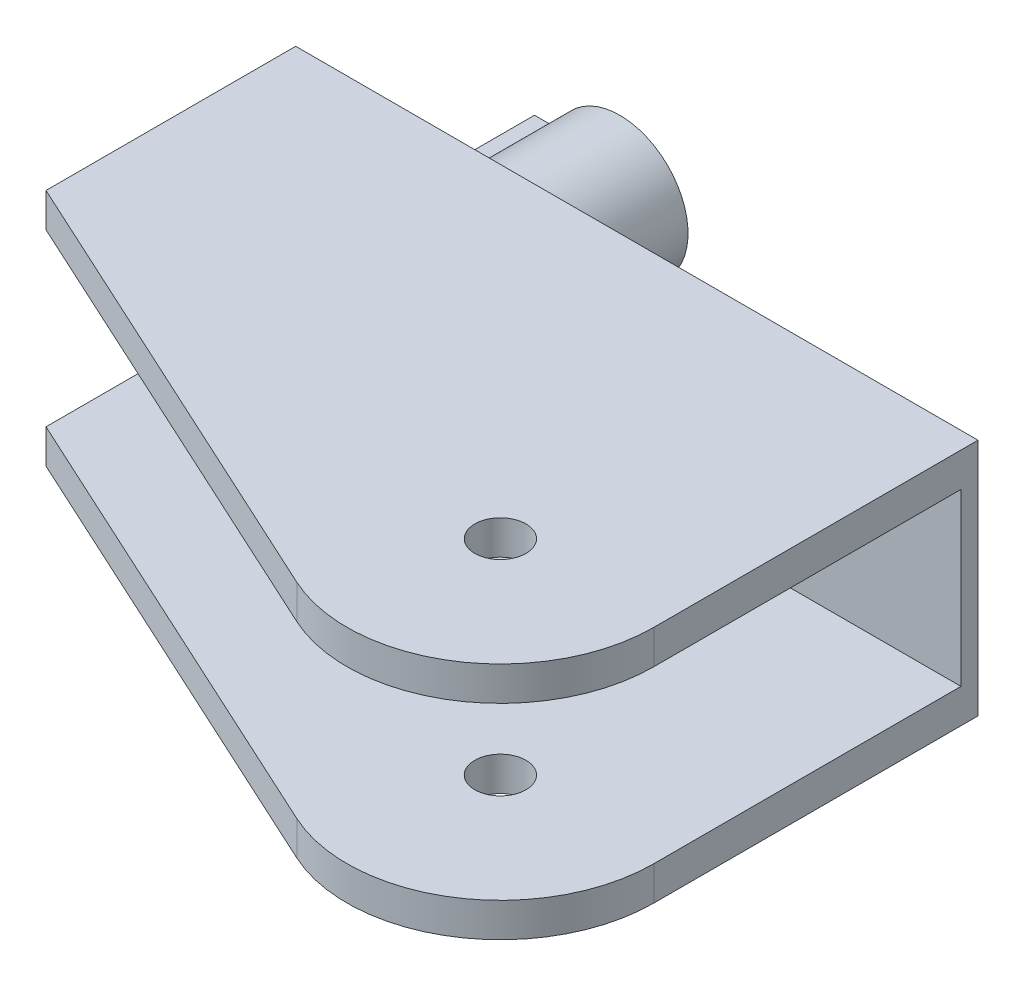
SolidWorks part; units mm, degrees
note: '?' marks a value the reader was unsure of. The reader was unsure of these and kept them because the rebuilt part matched: shared geometry of "草图1<2>".
ref_plane "前视基准面" through (0, 0, 0) normal (0, 0, 1) x (1, 0, 0)
ref_plane "上视基准面" through (0, 0, 0) normal (0, 1, 0) x (1, 0, 0)
ref_plane "右视基准面" through (0, 0, 0) normal (1, 0, 0) x (0, 0, -1)
other "Configuration Table"
sketch "草图1" plane through (0, 0, 0) normal (0, 1, 0) x (1, 0, 0)
  line L0 (45, 0) -> (45, 90)
  line L1 (45, 90) -> (-155, 90)
  line L2 (-155, 90) -> (-155, 21.8046)
  line L3 (-155, 21.8046) -> (-18.815, -40.8778)
  arc A0 (-18.815, -40.8778) -> (45, 0) centre (0, 0) ccw
  circle A1 centre (0, 0) radius 7.5
  dimension "D1" = 15
  dimension "D2" = 90
  dimension "D3" = 200
  dimension "D4" = 90
extrude "凸台-拉伸1" add sketch "草图1" along normal blind 10
ref_plane "基准面1" through (0, -25, 0) normal (0, -1, 0) x (-1, 0, 0)
sketch "草图3" plane through (45, 0, 0) normal (1, 0, 0) x (0, 0, -1)
  line L0 (-74.25, -25) -> (74.25, -25) construction
  line L5 (90, 10) -> (95, 10)
  line L6 (90, 10) -> (90, -25)
  line L7 (90, -25) -> (95, -25)
  line L8 (95, 10) -> (95, -25)
  dimension "D1" = 5
extrude "凸台-拉伸2" add sketch "草图3" against normal blind 200 contours L5 L8 L7 L6
mirror "镜向5" about plane through (0, -25, 0) normal (0, -1, 0) of "凸台-拉伸1", "凸台-拉伸2"
extrude "凸台-拉伸3" add sketch "草图1<2>" against normal up to surface (60 mm away) up to face at (-55, -60, -92.5)
sketch "草图1<2>" plane through (0, 0, 0) normal (0, 1, 0) x (1, 0, 0) same geometry as "草图1"
sketch "草图7" plane through (45, 0, 0) normal (1, 0, 0) x (0, 0, -1)
  line L0 (-45, 10) -> (-45, -60) construction
  line L1 (-45, 0) -> (90, 0)
  line L2 (-45, 0) -> (-45, -50)
  line L3 (-45, -50) -> (90, -50)
  line L4 (90, 0) -> (90, -50)
  line L5 (0, 10) -> (-45, 10) construction
  line L6 (95, 10) -> (95, -60) construction
  line L7 (-45, -60) -> (0, -60) construction
  dimension "D1" = 10
  dimension "D2" = 5
  dimension "D3" = 10
extrude "切除-拉伸1" cut sketch "草图7" against normal through all
ref_axis "基准轴1" through (0, 39.0625, 0) along (0, -1, 0)?
sketch "草图8" plane through (0, 0, -95) normal (0, 0, -1) x (-1, 0, 0)
  line L0 (-45, -25) -> (155, -25) construction
  line L1 (-45, 10) -> (-45, -60) construction
  line L2 (155, 10) -> (155, -60) construction
  line L4 (123.5405, -17.5) -> (130, -17.5)
  line L6 (123.5405, -32.5) -> (130, -32.5)
  line L7 (130, -17.5) -> (130, -32.5)
  arc A0 (123.5405, -17.5) -> (123.5405, -32.5) centre (105, -25) ccw
  point P8 (55, -25)
  point P9 (125, -25)
  dimension "D1" = 40
  dimension "D2" = 50
  dimension "D3" = 5
  dimension "D4" = 15
  dimension "D5" = 6.4595
extrude "凸台-拉伸4" add sketch "草图8" along normal blind 45
ref_axis "基准轴2" through (-105, -25, -210.7376) along (0, 0, 1)?
